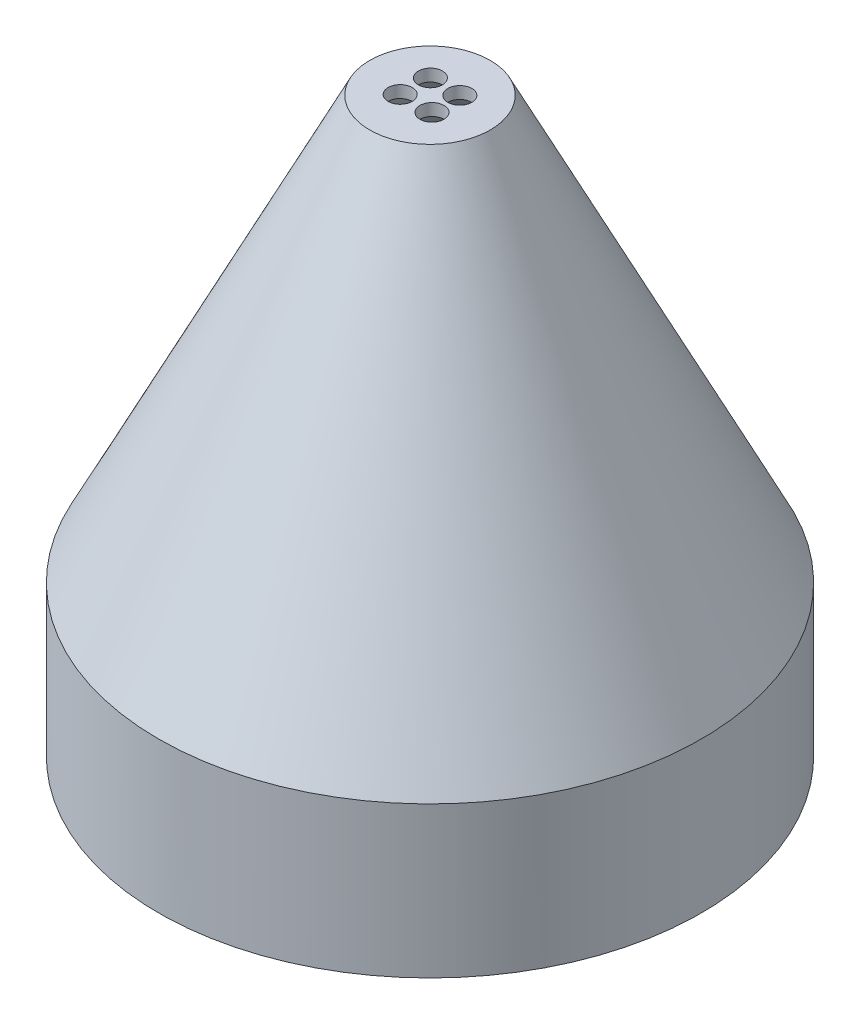
SolidWorks part; units mm, degrees
ref_plane "前视基准面" through (0, 0, 0) normal (0, 0, 1) x (1, 0, 0)
ref_plane "上视基准面" through (0, 0, 0) normal (0, 1, 0) x (1, 0, 0)
ref_plane "右视基准面" through (0, 0, 0) normal (1, 0, 0) x (0, 0, -1)
sketch "草图1" plane through (0, 0, 0) normal (0, 1, 0) x (1, 0, 0)
  circle A0 centre (0, 0) radius 45
  circle A1 centre (0, 0) radius 43.5
  point P4 (-45, 0)
extrude "凸台-拉伸1" add sketch "草图1" along normal blind 25
sketch "草图2" plane through (0, 0, 0) normal (0, 1, 0) x (1, 0, 0)
  line L0 (-45, 0) -> (-53, 0)
  line L1 (-16.2155, 41.9769) -> (-16.1176, 42.0145)
  line L2 (-16.1176, 42.0145) -> (-18.9917, 49.4804)
  circle A0 centre (0, 0) radius 45 construction
  arc A1 (-53, 0) -> (-18.9917, 49.4804) centre (-7.1191, 4.893) cw
  arc A2 (-16.1176, 42.0145) -> (-45, 0) centre (0, 0) ccw
extrude "凸台-拉伸2" add sketch "草图2" along normal blind 3 contours A2 L0 A1 L2
sketch "草图5" plane through (0, 0, 0) normal (0, 0, 1) x (1, 0, 0)
  line L0 (-45, 25) -> (0, 25)
  line L1 (43.5, 25) -> (-43.5, 25) construction
  line L2 (0, 25) -> (0, 95)
  line L3 (0, 95) -> (-10, 95)
  line L5 (-45, 25) -> (-10, 95)
revolve "旋转3" add sketch "草图5" angle 360 about L2
shell "抽壳9" thickness 2 removed face at (0, 25, 43.5)
sketch "草图6" plane through (0, 93, 0) normal (0, -1, 0) x (1, 0, 0)
  circle A1 centre (-2.5744, 2.3711) radius 2
  circle A2 centre (2.6321, 2.307) radius 2
  circle A3 centre (-2.4435, -2.5059) radius 2
  circle A4 centre (2.5048, -2.4445) radius 2
extrude "切除-拉伸1" cut sketch "草图6" against normal blind 3 contours A1 | A2 | A3 | A4
